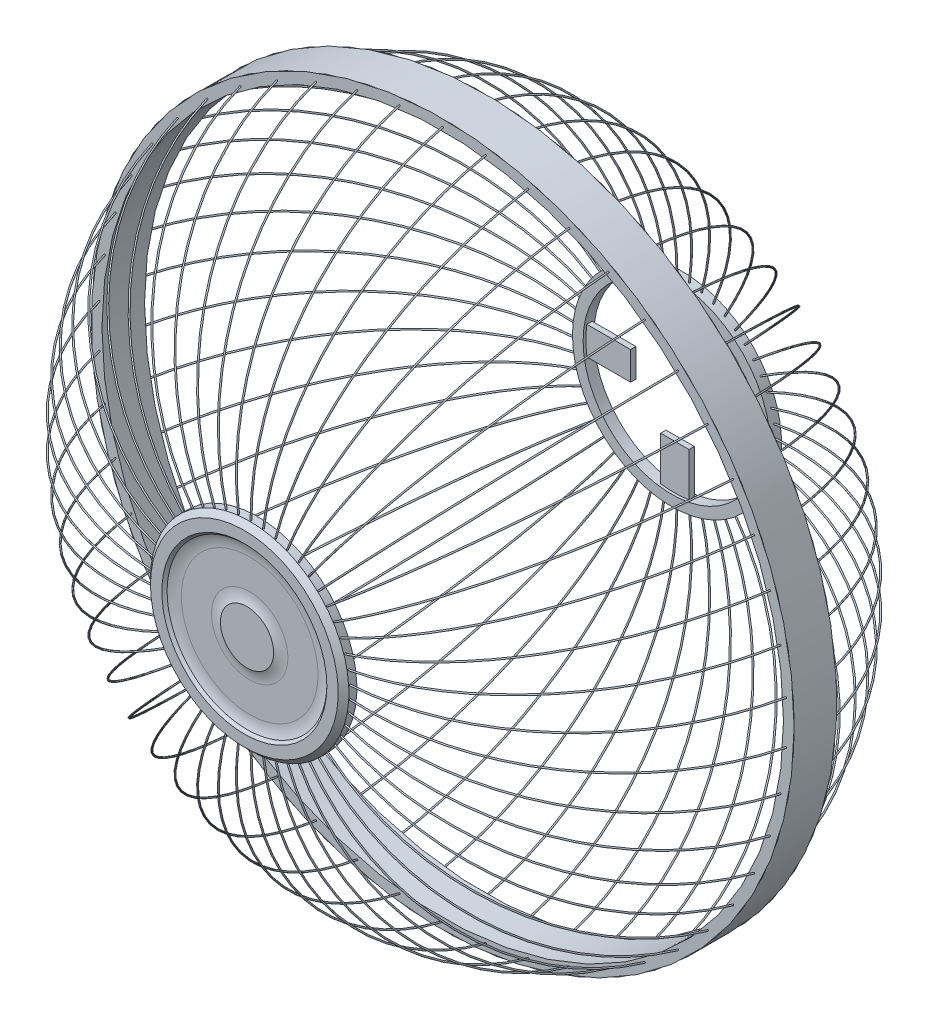
SolidWorks part; units mm, degrees
ref_plane "Front Plane" through (0, 0, 0) normal (0, 0, 1) x (1, 0, 0)
ref_plane "Top Plane" through (0, 0, 0) normal (0, 1, 0) x (1, 0, 0)
ref_plane "Right Plane" through (0, 0, 0) normal (1, 0, 0) x (0, 0, -1)
sketch "Sketch1" plane through (0, 0, 0) normal (0, 0, 1) x (1, 0, 0)
  circle A0 centre (0, 0) radius 165.1
  dimension "D1" = 330.2
extrude "Extrude-Thin1" add sketch "Sketch1" along normal mid plane 20.32 thin thin type mid plane wall 5.08
ref_plane "Plane1" through (0, 0, 101.6) normal (0, 0, 1) x (1, 0, 0)
sketch "Sketch2" plane through (0, 0, 101.6) normal (0, 0, 1) x (1, 0, 0)
  circle A0 centre (0, 0) radius 47.3256
extrude "Boss-Extrude1" add sketch "Sketch2" along normal mid plane 6.35 separate body
sketch "Sketch4" plane through (0, 0, 0) normal (1, 0, 0) x (0, 0, -1)
  line L0 (-10.16, 167.64) -> (-10.16, -167.64) construction
  line L2 (-98.425, 47.3256) -> (-104.775, 47.3256) construction
  arc A1 (-10.16, 164.0896) -> (-101.6, 47.3256) centre (17.778, 48.0247) ccw
  dimension "D2" = 164.0896
  dimension "D1" = 119.38
ref_plane "Plane5" through (0, 47.3256, 101.6) normal (0, 1, 0) x (1, 0, 0)
sketch "Sketch10" plane through (0, 47.3256, 101.6) normal (0, 1, 0) x (1, 0, 0)
  circle A0 centre (0, 0) radius 0.3175
  dimension "D1" = 0.635
sweep "Sweep5" add profiles "Sketch10" path "Sketch4"
sketch "Sketch11" plane through (0, 6.296, -26.8462) normal (0, 0.2283, -0.9736) x (-1, 0, 0)
  line L1 (-0.3175, 162.0749) -> (0.3175, 162.0749)
  line L2 (-0.3175, 162.0749) -> (0.3175, 162.0749)
  arc A2 (0.3175, 162.0749) -> (-0.3175, 162.0749) centre (0, 162.0749) ccw
  arc A3 (0.3175, 162.0749) -> (-0.3175, 162.0749) centre (0, 162.0749) ccw
  dimension "D1" = 0
ref_axis "Axis1" through (0, 243.078, 0) along (0, -1, 0)
ref_plane "Plane7" through (0, 0, -101.6) normal (0, 0, 1) x (1, 0, 0)
sketch "Sketch12" plane through (0, 0, -101.6) normal (0, 0, 1) x (1, 0, 0)
  circle A0 centre (0, 0) radius 47.3256
  circle A1 centre (0, 0) radius 47.3256 construction
extrude "Extrude-Thin2" add sketch "Sketch12" along normal mid plane 5.08 separate body thin thin type one direction reverse wall 5.08
chamfer "Chamfer1" distance 2.54 angle 45 1 edges at (47.3256, 0, 104.775)
sketch "Sketch13" plane through (0, 0, 104.775) normal (0, 0, 1) x (1, 0, 0)
  circle A0 centre (0, 0) radius 38.1
  dimension "D1" = 76.2
extrude "Cut-Extrude1" cut sketch "Sketch13" against normal blind 2.54
chamfer "Chamfer2" distance 1.27 angle 45 1 edges at (38.1, 0, 104.775)
sketch "Sketch14" plane through (0, 0, 102.235) normal (0, 0, 1) x (1, 0, 0)
  circle A0 centre (0, 0) radius 12.7
  dimension "D1" = 25.4
extrude "Boss-Extrude3" add sketch "Sketch14" along normal blind 1.27
fillet "Fillet1" radius 12.7 1 edges at (12.7, 0, 102.235)
fillet "Fillet2" radius 12.7 1 edges at (38.1, 0, 102.235)
pattern_circular "CirPattern1" count 50 over 360 about axis through (0, 0, 10.16) along (0, 0, 1) of "Sweep5"
pattern_circular "CirPattern2" count 2 every 180 about axis through (0, 243.078, 0) along (0, -1, 0) of "CirPattern1"
sketch "Sketch15" plane through (0, 0, -101.6) normal (0, 0, 1) x (1, 0, 0)
  line L0 (6.5115, 41.7407) -> (6.5115, 20.8587)
  line L1 (6.5115, 20.8587) -> (-6.984, 20.8587)
  line L2 (-6.984, 20.8587) -> (-6.984, 41.6643)
  line L4 (0, 0) -> (-0.3175, 56.035) construction
  line L5 (-0.3175, 164.0896) -> (-0.3175, 47.3256) construction
  circle A0 centre (0, 0) radius 42.2456 construction
  arc A1 (6.5115, 41.7407) -> (-6.984, 41.6643) centre (0, 0) ccw
  dimension "D1" = 20.8587
  dimension "D2" = 13.4955
  dimension "D3" = 6.5115
extrude "Boss-Extrude4" add sketch "Sketch15" along normal mid plane 2.54
pattern_circular "CirPattern4" count 4 over 360 about axis through (0, 0, -99.06) along (0, 0, 1) of "Boss-Extrude4"
